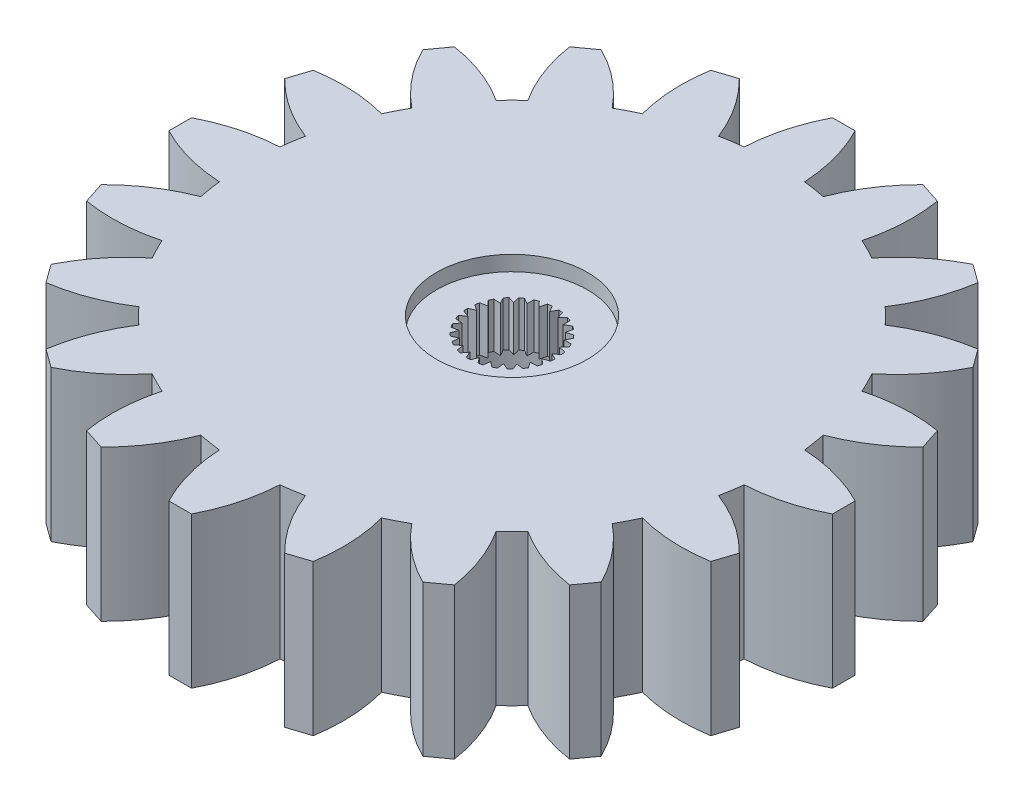
SolidWorks part; units mm, degrees
ref_plane "Front Plane" through (0, 0, 0) normal (0, 0, 1) x (1, 0, 0)
ref_plane "Top Plane" through (0, 0, 0) normal (0, 1, 0) x (1, 0, 0)
ref_plane "Right Plane" through (0, 0, 0) normal (1, 0, 0) x (0, 0, -1)
sketch "Sketch2" plane through (0, 0, 0) normal (0, 1, 0) x (1, 0, 0)
  line L0 (0, -10.2886) -> (0, 10.2886) construction
  line L1 (0, 0) -> (0.6267, 4.1579) construction
  line L2 (0, 0) -> (-0.6267, 4.1579) construction
  line L3 (0, 0) -> (1.373, 17.4461) construction
  line L4 (0, 0) -> (-1.373, 17.4461) construction
  line L5 (-0.2259, 2.8912) -> (0, 2.5)
  line L6 (0, 2.5) -> (0.2259, 2.8912)
  line L7 (-0.75, 21.9872) -> (0.75, 21.9872)
  line L8 (0.6217, 2.4215) -> (0.9378, 2.7442)
  line L9 (7.8676, 46.3212) -> (7.9539, 46.8293)
  line L10 (3.8992, 46.8226) -> (3.9419, 47.3362)
  line L11 (0.5003, 2.8565) -> (0.6217, 2.4215)
  line L12 (13.6112, 44.9699) -> (13.7605, 45.4632)
  line L13 (9.7368, 45.9647) -> (9.8436, 46.4688)
  line L14 (1.2044, 2.1908) -> (1.5908, 2.4248)
  line L15 (19.1401, 42.9094) -> (19.35, 43.38)
  line L16 (15.421, 44.3819) -> (15.5901, 44.8687)
  line L17 (1.1949, 2.6424) -> (1.2044, 2.1908)
  line L18 (24.3671, 40.1721) -> (24.6344, 40.6128)
  line L19 (20.8619, 42.0991) -> (21.0907, 42.5609)
  line L20 (1.7114, 1.8224) -> (2.1438, 1.953)
  line L21 (29.2099, 36.8013) -> (29.5303, 37.205)
  line L22 (25.9738, 39.1525) -> (26.2587, 39.5819)
  line L23 (1.8145, 2.2622) -> (1.7114, 1.8224)
  line L24 (33.592, 32.8502) -> (33.9604, 33.2105)
  line L25 (30.6761, 35.5884) -> (31.0126, 35.9787)
  line L26 (2.1108, 1.3396) -> (2.5621, 1.3585)
  line L27 (37.4443, 28.381) -> (37.855, 28.6923)
  line L28 (34.8946, 31.463) -> (35.2774, 31.8081)
  line L29 (2.3201, 1.7399) -> (2.1108, 1.3396)
  line L30 (40.7061, 23.4641) -> (41.1526, 23.7215)
  line L31 (38.5628, 26.8415) -> (38.9858, 27.1359)
  line L32 (2.3776, 0.7725) -> (2.8195, 0.6786)
  line L33 (43.326, 18.1773) -> (43.8012, 18.3767)
  line L34 (41.6229, 21.7966) -> (42.0794, 22.0357)
  line L35 (2.6799, 1.1082) -> (2.3776, 0.7725)
  line L36 (45.2626, 12.6038) -> (45.7591, 12.742)
  line L37 (44.0265, 16.408) -> (44.5094, 16.588)
  line L38 (2.4951, 0.157) -> (2.8997, -0.0439)
  line L39 (46.4853, 6.8315) -> (46.9952, 6.9064)
  line L40 (45.7358, 10.7606) -> (46.2375, 10.8787)
  line L41 (2.8713, 0.4069) -> (2.4951, 0.157)
  line L42 (46.975, 0.9515) -> (47.4903, 0.9619)
  line L43 (46.7238, 4.9436) -> (47.2363, 4.9978)
  line L44 (2.4557, -0.4685) -> (2.7977, -0.7636)
  line L45 (46.7238, -4.9436) -> (47.2363, -4.9978)
  line L46 (46.975, -0.9515) -> (47.4903, -0.9619)
  line L47 (2.8823, -0.3199) -> (2.4557, -0.4685)
  line L48 (45.7358, -10.7606) -> (46.2375, -10.8787)
  line L49 (46.4853, -6.8315) -> (46.9952, -6.9064)
  line L50 (2.2621, -1.0644) -> (2.5199, -1.4354)
  line L51 (44.0265, -16.408) -> (44.5094, -16.588)
  line L52 (45.2626, -12.6038) -> (45.7591, -12.742)
  line L53 (2.7122, -1.0267) -> (2.2621, -1.0644)
  line L54 (41.6229, -21.7966) -> (42.0794, -22.0357)
  line L55 (43.326, -18.1773) -> (43.8012, -18.3767)
  line L56 (1.9263, -1.5936) -> (2.0837, -2.0169)
  line L57 (38.5628, -26.8415) -> (38.9858, -27.1359)
  line L58 (40.7061, -23.4641) -> (41.1526, -23.7215)
  line L59 (2.3717, -1.6689) -> (1.9263, -1.5936)
  line L60 (34.8946, -31.463) -> (35.2774, -31.8081)
  line L61 (37.4443, -28.381) -> (37.855, -28.6923)
  line L62 (1.4695, -2.0225) -> (1.5167, -2.4718)
  line L63 (30.6761, -35.5884) -> (31.0126, -35.9787)
  line L64 (33.592, -32.8502) -> (33.9604, -33.2105)
  line L65 (1.8821, -2.2063) -> (1.4695, -2.0225)
  line L66 (25.9738, -39.1525) -> (26.2587, -39.5819)
  line L67 (29.2099, -36.8013) -> (29.5303, -37.205)
  line L68 (0.9203, -2.3244) -> (0.8543, -2.7713)
  line L69 (20.8619, -42.0991) -> (21.0907, -42.5609)
  line L70 (24.3671, -40.1721) -> (24.6344, -40.6128)
  line L71 (1.2743, -2.605) -> (0.9203, -2.3244)
  line L72 (15.421, -44.3819) -> (15.5901, -44.8687)
  line L73 (19.1401, -42.9094) -> (19.35, -43.38)
  line L74 (0.3133, -2.4803) -> (0.1383, -2.8967)
  line L75 (9.7368, -45.9647) -> (9.8436, -46.4688)
  line L76 (13.6112, -44.9699) -> (13.7605, -45.4632)
  line L77 (0.5864, -2.8401) -> (0.3133, -2.4803)
  line L78 (3.8992, -46.8226) -> (3.9419, -47.3362)
  line L79 (7.8676, -46.3212) -> (7.9539, -46.8293)
  line L80 (-0.3133, -2.4803) -> (-0.5864, -2.8401)
  line L81 (-2, -46.942) -> (-2.0219, -47.4569)
  line L82 (2, -46.942) -> (2.0219, -47.4569)
  line L83 (-0.1383, -2.8967) -> (-0.3133, -2.4803)
  line L84 (-7.8676, -46.3212) -> (-7.9539, -46.8293)
  line L85 (-3.8992, -46.8226) -> (-3.9419, -47.3362)
  line L86 (-0.9203, -2.3244) -> (-1.2743, -2.605)
  line L87 (-13.6112, -44.9699) -> (-13.7605, -45.4632)
  line L88 (-9.7368, -45.9647) -> (-9.8436, -46.4688)
  line L89 (-0.8543, -2.7713) -> (-0.9203, -2.3244)
  line L90 (-19.1401, -42.9094) -> (-19.35, -43.38)
  line L91 (-15.421, -44.3819) -> (-15.5901, -44.8687)
  line L92 (-1.4695, -2.0225) -> (-1.8821, -2.2063)
  line L93 (-24.3671, -40.1721) -> (-24.6344, -40.6128)
  line L94 (-20.8619, -42.0991) -> (-21.0907, -42.5609)
  line L95 (-1.5167, -2.4718) -> (-1.4695, -2.0225)
  line L96 (-29.2099, -36.8013) -> (-29.5303, -37.205)
  line L97 (-25.9738, -39.1525) -> (-26.2587, -39.5819)
  line L98 (-1.9263, -1.5936) -> (-2.3717, -1.6689)
  line L99 (-33.592, -32.8502) -> (-33.9604, -33.2105)
  line L100 (-30.6761, -35.5884) -> (-31.0126, -35.9787)
  line L101 (-2.0837, -2.0169) -> (-1.9263, -1.5936)
  line L102 (-37.4443, -28.381) -> (-37.855, -28.6923)
  line L103 (-34.8946, -31.463) -> (-35.2774, -31.8081)
  line L104 (-2.2621, -1.0644) -> (-2.7122, -1.0267)
  line L105 (-40.7061, -23.4641) -> (-41.1526, -23.7215)
  line L106 (-38.5628, -26.8415) -> (-38.9858, -27.1359)
  line L107 (-2.5199, -1.4354) -> (-2.2621, -1.0644)
  line L108 (-43.326, -18.1773) -> (-43.8012, -18.3767)
  line L109 (-41.6229, -21.7966) -> (-42.0794, -22.0357)
  line L110 (-2.4557, -0.4685) -> (-2.8823, -0.3199)
  line L111 (-45.2626, -12.6038) -> (-45.7591, -12.742)
  line L112 (-44.0265, -16.408) -> (-44.5094, -16.588)
  line L113 (-2.7977, -0.7636) -> (-2.4557, -0.4685)
  line L114 (-46.4853, -6.8315) -> (-46.9952, -6.9064)
  line L115 (-45.7358, -10.7606) -> (-46.2375, -10.8787)
  line L116 (-2.4951, 0.157) -> (-2.8713, 0.4069)
  line L117 (-46.975, -0.9515) -> (-47.4903, -0.9619)
  line L118 (-46.7238, -4.9436) -> (-47.2363, -4.9978)
  line L119 (-2.8997, -0.0439) -> (-2.4951, 0.157)
  line L120 (-46.7238, 4.9436) -> (-47.2363, 4.9978)
  line L121 (-46.975, 0.9515) -> (-47.4903, 0.9619)
  line L122 (-2.3776, 0.7725) -> (-2.6799, 1.1082)
  line L123 (-45.7358, 10.7606) -> (-46.2375, 10.8787)
  line L124 (-46.4853, 6.8315) -> (-46.9952, 6.9064)
  line L125 (-2.8195, 0.6786) -> (-2.3776, 0.7725)
  line L126 (-44.0265, 16.408) -> (-44.5094, 16.588)
  line L127 (-45.2626, 12.6038) -> (-45.7591, 12.742)
  line L128 (-2.1108, 1.3396) -> (-2.3201, 1.7399)
  line L129 (-41.6229, 21.7966) -> (-42.0794, 22.0357)
  line L130 (-43.326, 18.1773) -> (-43.8012, 18.3767)
  line L131 (-2.5621, 1.3585) -> (-2.1108, 1.3396)
  line L132 (-38.5628, 26.8415) -> (-38.9858, 27.1359)
  line L133 (-40.7061, 23.4641) -> (-41.1526, 23.7215)
  line L134 (-1.7114, 1.8224) -> (-1.8145, 2.2622)
  line L135 (-34.8946, 31.463) -> (-35.2774, 31.8081)
  line L136 (-37.4443, 28.381) -> (-37.855, 28.6923)
  line L137 (-2.1438, 1.953) -> (-1.7114, 1.8224)
  line L138 (-30.6761, 35.5884) -> (-31.0126, 35.9787)
  line L139 (-33.592, 32.8502) -> (-33.9604, 33.2105)
  line L140 (-1.2044, 2.1908) -> (-1.1949, 2.6424)
  line L141 (-25.9738, 39.1525) -> (-26.2587, 39.5819)
  line L142 (-29.2099, 36.8013) -> (-29.5303, 37.205)
  line L143 (-1.5908, 2.4248) -> (-1.2044, 2.1908)
  line L144 (-20.8619, 42.0991) -> (-21.0907, 42.5609)
  line L145 (-24.3671, 40.1721) -> (-24.6344, 40.6128)
  line L146 (-0.6217, 2.4215) -> (-0.5003, 2.8565)
  line L147 (-15.421, 44.3819) -> (-15.5901, 44.8687)
  line L148 (-19.1401, 42.9094) -> (-19.35, 43.38)
  line L149 (-0.9378, 2.7442) -> (-0.6217, 2.4215)
  line L150 (-9.7368, 45.9647) -> (-9.8436, 46.4688)
  line L151 (-13.6112, 44.9699) -> (-13.7605, 45.4632)
  line L153 (-3.8992, 46.8226) -> (-3.9419, 47.3362)
  line L154 (-7.8676, 46.3212) -> (-7.9539, 46.8293)
  circle A0 centre (0, 0) radius 18.7939 construction
  circle A1 centre (0, 0) radius 2.5 construction
  circle A2 centre (0, 0) radius 2.9
  circle A24 centre (0, 0) radius 17.5
  circle A25 centre (0, 0) radius 20 construction
  circle A26 centre (0, 0) radius 22 construction
  arc A27 (0.75, 21.9872) -> (2, 17.3853) centre (-9.2545, 16.799) cw
  arc A28 (-0.75, 21.9872) -> (-2, 17.3853) centre (9.2545, 16.799) ccw
  point P7 (0, 0)
  point P30 (1.5692, 19.9383)
  point P78 (0, 0)
  point P139 (0, 0)
  point P226 (0, 0)
  dimension "D1" = 5
  dimension "D3" = 5.8
  dimension "D5" = 37.5877
  dimension "D6" = 35
  dimension "D7" = 40
  dimension "D8" = 44
  dimension "D2" = 8.571
  dimension "D9" = 4.5
  dimension "D11" = 1.5
  dimension "D12" = 4
  dimension "D4" = 60
  dimension "D10" = 30
  dimension "D13" = 25
extrude "Boss-Extrude1" add sketch "Sketch2" along normal blind 10 contours A24 | A2 region at (0, 0, -17.005)
extrude "Boss-Extrude2" add sketch "Sketch2<4>" along normal up to surface (10 mm away) contours L7 A28 A24 A27 region at (0, 0, -19.4231) up to face at (0, 10, 17.5)
sketch "Sketch2<4>" plane through (0, 0, 0) normal (0, 1, 0) x (1, 0, 0) same geometry as "Sketch2"
pattern_circular "CirPattern1" count 20 over 360 about axis through (0, 10, 0) along (0, 1, 0) of "Boss-Extrude2"
extrude "Cut-Extrude2" cut sketch "Sketch2<7>" against normal blind 4 from surface contours L77 A2 L68 L71 L62 L65 L56 L59 L50 L53 L44 L47 L38 L41 L32 L35 L26 L29 L20 L23 L14 L17 L8 L11 L6 L5 L146 L149 L140 L143 L134 L137 L128 L131 L122 region at (0, 0, 0) starting at face at (0, 10, 0)
sketch "Sketch2<7>" plane through (0, 0, 0) normal (0, 1, 0) x (1, 0, 0) same geometry as "Sketch2"
sketch "Sketch3" plane through (0, 0, 0) normal (0, -1, 0) x (1, 0, 0)
  circle A0 centre (0, 0) radius 5
  dimension "D1" = 10
extrude "Cut-Extrude3" cut sketch "Sketch3" against normal up to surface (6 mm away) up to face at (0, 6, 0)
sketch "Sketch4" plane through (0, 10, 0) normal (0, 1, 0) x (1, 0, 0)
  circle A0 centre (0, 0) radius 5
  dimension "D1" = 10
extrude "Cut-Extrude4" cut sketch "Sketch4" against normal blind 1
equation "\"Module\"= 2"
equation "\"Teeth\"= 20"
equation "\"Pitch Diameter\"= \"Module\" * \"Teeth\""
equation "\"Outer Diamter\"= \"Pitch Diameter\" + ( 2 * \"Module\" )"
equation "\"Root Diameter\"= \"Pitch Diameter\" - ( 2.5 * \"Module\" )"
equation "\"Base Diamter\"= \"Pitch Diameter\" * cos ( 20 )"
equation "\"D5@Sketch2\"=\"Base Diamter\""
equation "\"D6@Sketch2\"=\"Root Diameter\""
equation "\"D8@Sketch2\"=\"Outer Diamter\""
equation "\"D9@Sketch2\"=90 / \"Teeth\""
equation "\"D7@Sketch2\"=\"Pitch Diameter\""
equation "\"D1@CirPattern1\"=\"Teeth\""
